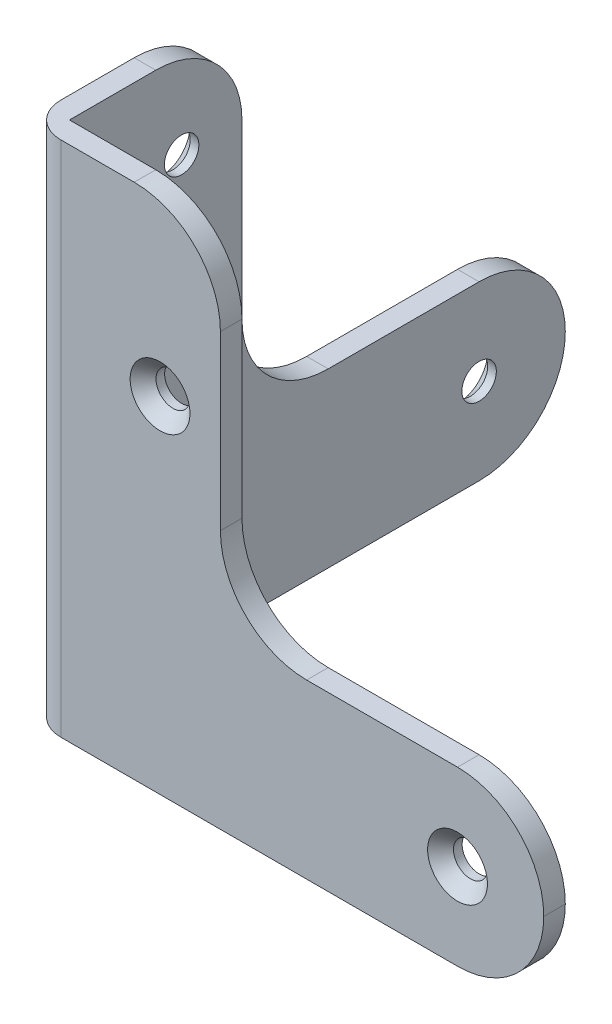
SolidWorks part; units mm, degrees
ref_plane "Front" through (0, 0, 0) normal (0, 0, 1) x (1, 0, 0)
ref_plane "Top" through (0, 0, 0) normal (0, 1, 0) x (1, 0, 0)
ref_plane "Right" through (0, 0, 0) normal (1, 0, 0) x (0, 0, -1)
sketch "Sketch1" plane through (0, 0, 0) normal (0, 1, 0) x (1, 0, 0)
  line L0 (0, 76.2) -> (0, 0)
  line L1 (0, 0) -> (76.2, 0)
  line L2 (76.2, 0) -> (76.2, 3.175)
  line L3 (76.2, 3.175) -> (3.175, 3.175)
  line L4 (3.175, 3.175) -> (3.175, 76.2)
  line L5 (3.175, 76.2) -> (0, 76.2)
  dimension "D1" = 3.175
  dimension "D2" = 76.2
extrude "Boss-Extrude1" add sketch "Sketch1" along normal blind 76.2
sketch "Sketch2" plane through (0, 0, -3.175) normal (0, 0, -1) x (-1, 0, 0)
  line L0 (-76.2, 0) -> (-3.175, 0) construction
  line L1 (-76.2, 76.2) -> (-28.575, 76.2)
  line L2 (-76.2, 76.2) -> (-76.2, 25.4)
  line L3 (-76.2, 25.4) -> (-28.575, 25.4)
  line L4 (-28.575, 76.2) -> (-28.575, 25.4)
  line L5 (-3.175, 76.2) -> (-3.175, 0) construction
  dimension "D1" = 25.4
  dimension "D2" = 25.4
extrude "Cut-Extrude1" cut sketch "Sketch2" against normal through all contours L4 L3 L2 L1
sketch "Sketch3" plane through (3.175, 0, 0) normal (1, 0, 0) x (0, 0, -1)
  line L0 (3.175, 76.2) -> (3.175, 0) construction
  line L1 (76.2, 76.2) -> (28.575, 76.2)
  line L2 (76.2, 76.2) -> (76.2, 25.4)
  line L3 (76.2, 25.4) -> (28.575, 25.4)
  line L4 (28.575, 76.2) -> (28.575, 25.4)
  line L5 (3.175, 0) -> (76.2, 0) construction
  dimension "D1" = 25.4
  dimension "D2" = 25.4
extrude "Cut-Extrude2" cut sketch "Sketch3" against normal through all
fillet "Fillet1" radius 5.08 1 edges at (0, 38.1, 0)
fillet "Fillet2" radius 12.7 8 edges at (1.5875, 76.2, -28.575) (1.5875, 25.4, -28.575) (1.5875, 25.4, -76.2) (1.5875, 0, -76.2) (76.2, 0, -1.5875) (76.2, 25.4, -1.5875) (28.575, 25.4, -1.5875) (28.575, 76.2, -1.5875)
sketch "Sketch4" plane through (0, 0, 0) normal (0, 0, 1) x (1, 0, 0)
  line L0 (28.575, 63.5) -> (28.575, 38.1) construction
  line L1 (5.08, 76.2) -> (15.875, 76.2) construction
  circle A0 centre (63.5, 12.7) radius 2.5
  arc A1 (76.2, 12.7) -> (63.5, 25.4) centre (63.5, 12.7) ccw construction
  circle A2 centre (19.685, 50.8) radius 2.5
  dimension "D1" = 5
  dimension "D2" = 8.89
  dimension "D3" = 25.4
extrude "Cut-Extrude3" cut sketch "Sketch4" against normal through all
sketch "Sketch5" plane through (0, 0, 0) normal (-1, 0, 0) x (0, 0, 1)
  line L0 (-28.575, 63.5) -> (-28.575, 38.1) construction
  line L1 (-15.875, 76.2) -> (-5.08, 76.2) construction
  circle A0 centre (-63.5, 12.7) radius 2.54
  circle A1 centre (-19.685, 63.5) radius 2.54
  arc A2 (-63.5, 25.4) -> (-76.2, 12.7) centre (-63.5, 12.7) ccw construction
  dimension "D1" = 8.89
  dimension "D2" = 12.7
  dimension "D3" = 5.08
extrude "Cut-Extrude4" cut sketch "Sketch5" against normal through all
chamfer "Chamfer1" distance 1.905 angle 45 4 edges at (66, 12.7, 0) (22.185, 50.8, 0) (0, 63.5, -17.145) (0, 12.7, -60.96)
